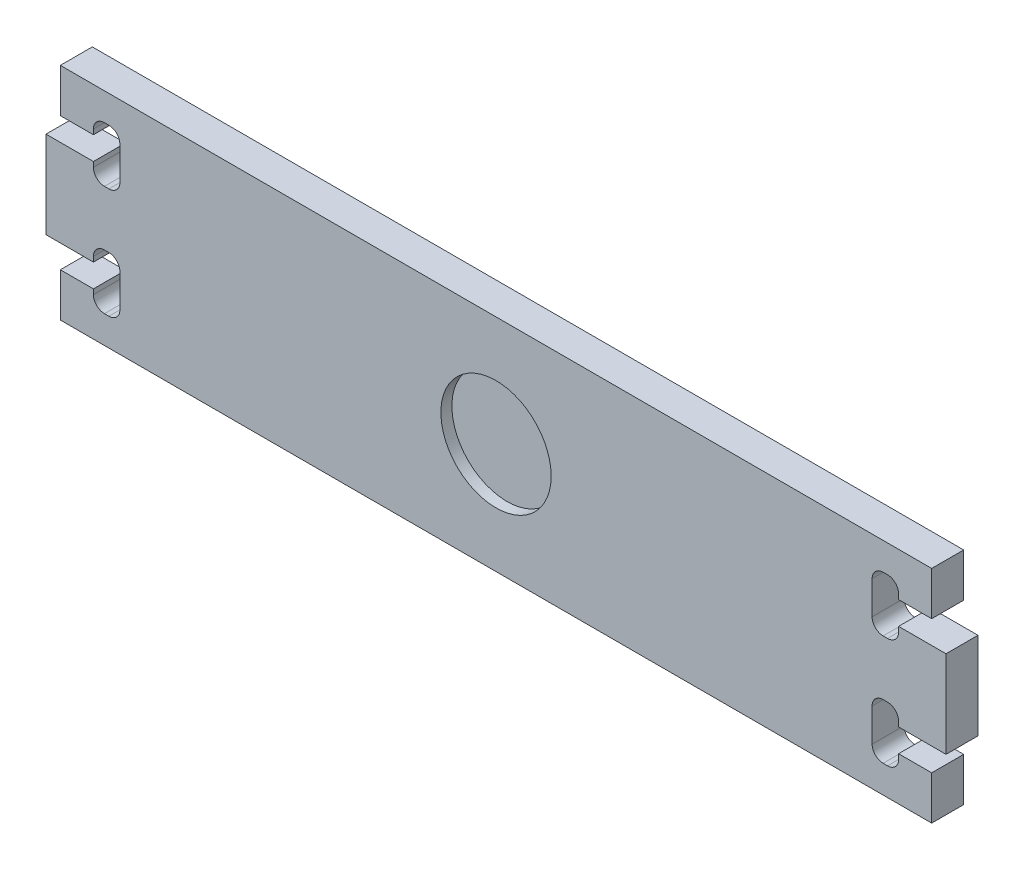
SolidWorks part; units mm, degrees
ref_plane "Front Plane" through (0, 0, 0) normal (0, 0, 1) x (1, 0, 0)
ref_plane "Top Plane" through (0, 0, 0) normal (0, 1, 0) x (1, 0, 0)
ref_plane "Right Plane" through (0, 0, 0) normal (1, 0, 0) x (0, 0, -1)
sketch "Sketch1" plane through (0, 0, 0) normal (0, 0, 1) x (1, 0, 0)
  line L0 (-39.5, 0) -> (39.5, 0) construction
  line L1 (-39.5, 10) -> (39.5, 10)
  line L2 (-39.5, 10) -> (-39.5, -10)
  line L3 (-39.5, -10) -> (39.5, -10)
  line L4 (39.5, 10) -> (39.5, -10)
  line L5 (-39.5, 10) -> (39.5, -10) construction
  line L6 (-39.5, -10) -> (39.5, 10) construction
  line L7 (0, 10) -> (0, -10) construction
  line L9 (-40.8, -3.95) -> (-39.5, -3.95)
  line L10 (-40.8, -3.95) -> (-40.8, 3.95)
  line L11 (-40.8, 3.95) -> (-39.5, 3.95)
  line L12 (-39.5, -3.95) -> (-39.5, 3.95)
  line L13 (-40.8, -3.95) -> (-39.5, 3.95) construction
  line L14 (-40.8, 3.95) -> (-39.5, -3.95) construction
  line L16 (40.8, 3.95) -> (39.5, 3.95)
  line L17 (40.8, -3.95) -> (40.8, 3.95)
  line L18 (40.8, -3.95) -> (39.5, -3.95)
  line L19 (-39.5, 5) -> (39.5, 5) construction
  line L20 (-35.3, 7.5) -> (-35.3, 2.5) construction
  line L21 (-36.5, 3.95) -> (-39.5, 3.95)
  line L22 (-36.5, 3.95) -> (-36.5, 6.05)
  line L23 (-36.5, 6.05) -> (-39.5, 6.05)
  line L24 (-39.5, 3.95) -> (-39.5, 6.05)
  line L25 (-36.5, 3.95) -> (-39.5, 6.05) construction
  line L26 (-36.5, 6.05) -> (-39.5, 3.95) construction
  line L27 (-34.1, 7.5) -> (-36.5, 7.5)
  line L28 (-34.1, 7.5) -> (-34.1, 2.5)
  line L29 (-34.1, 2.5) -> (-36.5, 2.5)
  line L30 (-36.5, 7.5) -> (-36.5, 2.5)
  line L31 (-34.1, 7.5) -> (-36.5, 2.5) construction
  line L32 (-34.1, 2.5) -> (-36.5, 7.5) construction
  line L33 (-34.1, -7.5) -> (-36.5, -7.5)
  line L34 (-34.1, -7.5) -> (-34.1, -2.5)
  line L35 (-34.1, -2.5) -> (-36.5, -2.5)
  line L36 (-36.5, -7.5) -> (-36.5, -2.5)
  line L37 (-36.5, -3.95) -> (-39.5, -3.95)
  line L38 (-36.5, -6.05) -> (-39.5, -6.05)
  line L39 (36.5, 3.95) -> (39.5, 3.95)
  line L40 (36.5, 6.05) -> (39.5, 6.05)
  line L41 (36.5, 7.5) -> (36.5, 2.5)
  line L42 (34.1, 7.5) -> (36.5, 7.5)
  line L43 (34.1, 7.5) -> (34.1, 2.5)
  line L44 (34.1, 2.5) -> (36.5, 2.5)
  line L45 (34.1, -2.5) -> (36.5, -2.5)
  line L46 (34.1, -7.5) -> (34.1, -2.5)
  line L47 (34.1, -7.5) -> (36.5, -7.5)
  line L48 (36.5, -7.5) -> (36.5, -2.5)
  line L49 (36.5, -6.05) -> (39.5, -6.05)
  line L50 (36.5, -3.95) -> (39.5, -3.95)
  point P0 (0, 0)
  point P10 (-40.15, 0)
  point P15 (-38, 5)
  point P35 (-35.3, 5)
  dimension "D1" = 79
  dimension "D2" = 20
  dimension "D4" = 1.3
  dimension "D7" = 5
  dimension "D8" = 2.1
  dimension "D9" = 3
  dimension "D10" = 2.4
  dimension "D11" = 5
extrude "Base shape" add sketch "Sketch1" along normal blind 2.9 contours L4 L1 L2 L3 | L9 L2 L11 L10 | L16 L4 L18 L17 region at (0, 0, 0) region at (-40.15, 0, 0) region at (40.15, 0, 0)
sketch "Sketch2" plane through (0, 0, 2.9) normal (0, 0, 1) x (1, 0, 0)
  circle A0 centre (0, 0) radius 5
  dimension "D1" = 10
extrude "Forward cut (temp)" cut sketch "Sketch2" against normal blind 1
fillet "Fillet1" radius 1 16 edges at (36.5, -7.5, 1.45) (36.5, 2.5, 1.45) (34.1, 2.5, 1.45) (34.1, -7.5, 1.45) (36.5, -2.5, 1.45) (36.5, 7.5, 1.45) (34.1, -2.5, 1.45) (34.1, 7.5, 1.45) (-36.5, -2.5, 1.45) (-34.1, -2.5, 1.45) (-34.1, -7.5, 1.45) (-36.5, -7.5, 1.45) (-36.5, 2.5, 1.45) (-34.1, 2.5, 1.45) (-34.1, 7.5, 1.45) (-36.5, 7.5, 1.45)
sketch "Sketch3" plane through (-40.8, 0, 0) normal (-1, 0, 0) x (0, 0, 1)
  line L0 (0, 6.05) -> (2.9, 3.95) construction
  line L1 (0, 6.05) -> (2.9, 6.05)
  line L2 (0, 6.05) -> (0, 3.95)
  line L3 (0, 3.95) -> (2.9, 3.95)
  line L4 (2.9, 6.05) -> (2.9, 3.95)
  line L5 (0, -3.95) -> (2.9, -6.05) construction
  line L6 (0, -3.95) -> (2.9, -3.95)
  line L7 (0, -3.95) -> (0, -6.05)
  line L8 (0, -6.05) -> (2.9, -6.05)
  line L9 (2.9, -3.95) -> (2.9, -6.05)
  point P6 (1.45, 5)
  point P13 (1.45, -5)
ref_axis "Tap axis top" through (-53.7846, 5, 1.45) along (1, 0, 0)
ref_axis "Tap axis bottom" through (-54.2844, -5, 1.45) along (1, 0, 0)
